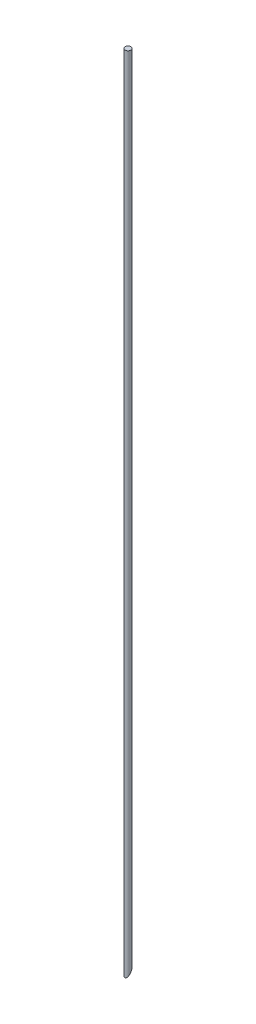
SolidWorks part; units mm, degrees
ref_plane "Front Plane" through (0, 0, 0) normal (0, 0, 1) x (1, 0, 0)
ref_plane "Top Plane" through (0, 0, 0) normal (0, 1, 0) x (1, 0, 0)
ref_plane "Right Plane" through (0, 0, 0) normal (1, 0, 0) x (0, 0, -1)
sketch "Sketch1" plane through (0, 0, 0) normal (0, 1, 0) x (1, 0, 0)
  circle A0 centre (0, 0) radius 0.11
  dimension "D1" = 0.22
extrude "Boss-Extrude1" add sketch "Sketch1" against normal blind 30 contours A0
sketch "Sketch3" plane through (0, 0, 0) normal (1, 0, 0) x (0, 0, -1)
  line L0 (-0.11, -30) -> (0.11, -29.6189)
  line L1 (0.11, -30) -> (0.11, 0) construction
  line L2 (0.11, -29.6189) -> (0.11, -30)
  line L3 (0.11, -30) -> (-0.11, -30)
  dimension "D1" = 60
extrude "Cut-Extrude1" cut sketch "Sketch3" against normal through all both and the other way through all
sketch "Sketch4" plane through (0, 0, 0) normal (0, 1, 0) x (1, 0, 0)
  line L1 (0, 0.11) -> (0, -0.11) construction
  circle A0 centre (0, 0) radius 0.11 construction
sketch "Sketch5" plane through (0, 0, 0) normal (1, 0, 0) x (0, 0, -1)
  line L0 (-0.11, -29.8189) -> (0.11, -29.8189) construction
  line L1 (-0.11, 0) -> (-0.11, -30) construction
  dimension "D1" = 0.2
